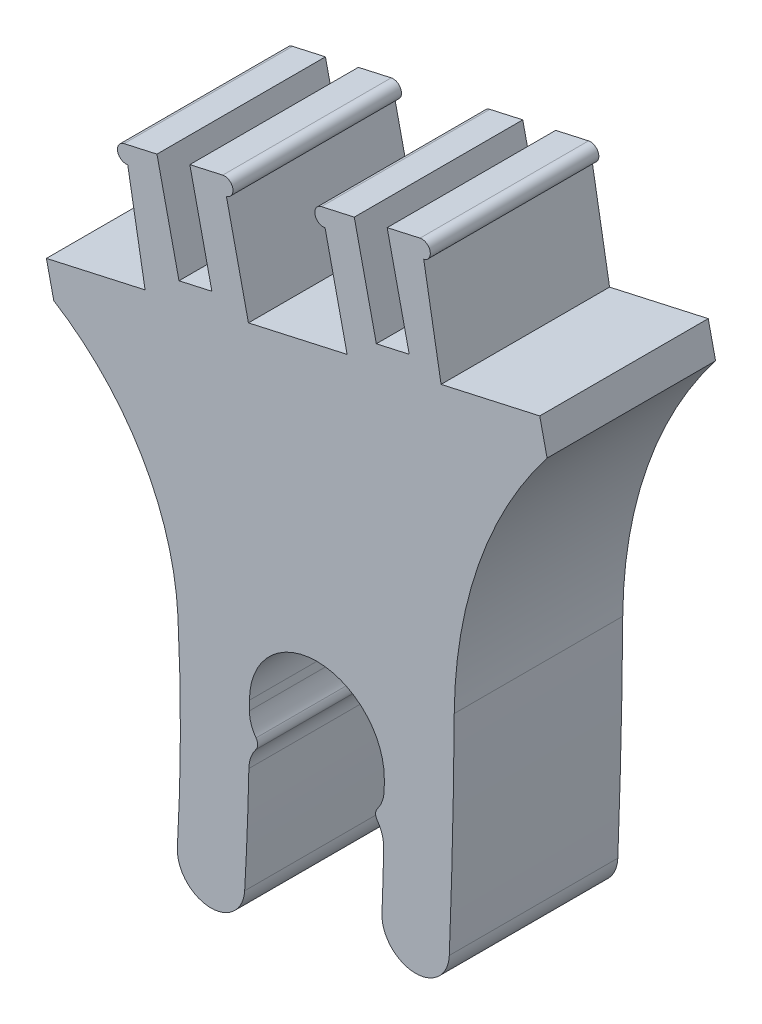
SolidWorks part; units mm, degrees
ref_plane "Front Plane" through (0, 0, 0) normal (0, 0, 1) x (1, 0, 0)
ref_plane "Top Plane" through (0, 0, 0) normal (0, 1, 0) x (1, 0, 0)
ref_plane "Right Plane" through (0, 0, 0) normal (1, 0, 0) x (0, 0, -1)
sketch "Sketch1" plane through (0, 0, 0) normal (0, 0, 1) x (1, 0, 0)
  line L0 (46.3286, 67.6651) -> (48.3537, 68.1177)
  line L1 (39.9639, 81.6128) -> (47.8164, 83.3676)
  line L3 (40.2311, 66.3025) -> (42.2676, 66.7576)
  arc A0 (46.4563, 72.4818) -> (46.4528, 71.6895) centre (-44.4563, 72.4818) cw
  arc A1 (46.4563, 72.4818) -> (42.4563, 72.4818) centre (44.4563, 72.4818) ccw
  arc A3 (42.2676, 66.7576) -> (42.447, 71.2127) centre (-44.4563, 72.4818) ccw
  arc A4 (47.8164, 83.3676) -> (48.3537, 68.1177) centre (-44.4563, 72.4818) cw
  arc A5 (40.2311, 66.3025) -> (39.9639, 81.6128) centre (-44.4563, 72.4818) ccw
  arc A6 (47.8164, 83.3676) -> (48.1264, 64.6591) centre (-44.4563, 72.4818) cw construction
  arc A7 (45.8301, 83.1333) -> (46.1335, 64.8275) centre (-44.4563, 72.4818) cw construction
  arc A8 (42.2258, 66.157) -> (41.9523, 81.8279) centre (-44.4563, 72.4818) ccw construction
  circle A9 centre (44.4563, 72.4818) radius 2 construction
  arc A10 (42.4529, 71.7127) -> (42.447, 71.2127) centre (42.4503, 71.4627) cw
  arc A11 (46.4528, 71.6895) -> (46.4471, 71.1896) centre (46.4503, 71.4395) ccw
  arc A12 (42.4529, 71.7127) -> (42.4563, 72.4818) centre (-44.4563, 72.4818) ccw
  arc A13 (46.4471, 71.1896) -> (46.3286, 67.6651) centre (-44.4563, 72.4818) cw
  dimension "D1" = 4
  dimension "D5" = 0.25
  dimension "D2" = 15
  dimension "D3" = 2
  dimension "D4" = 2
extrude "Boss-Extrude1" add sketch "Sketch1" along normal blind 5
fillet "Fillet1" radius 1 4 edges at (46.4471, 71.1896, 2.5) (46.4528, 71.6895, 2.5) (42.447, 71.2127, 2.5) (42.4529, 71.7127, 2.5)
fillet "Fillet2" radius 1 4 edges at (48.3537, 68.1177, 2.5) (46.3286, 67.6651, 2.5) (42.2676, 66.7576, 2.5) (40.2311, 66.3025, 2.5)
sketch "Sketch2" plane through (0, 0, 5) normal (0, 0, 1) x (1, 0, 0)
  line L1 (39.702, 79.5049) -> (38.8442, 84.4366)
  line L2 (42.4262, 82.1631) -> (41.772, 85.0908)
  line L3 (38.8442, 84.4366) -> (41.772, 85.0908)
  line L5 (48.4854, 81.4678) -> (47.6275, 86.3994)
  line L6 (45.354, 82.8173) -> (44.6998, 85.7451)
  line L7 (47.6275, 86.3994) -> (44.6998, 85.7451)
  line L8 (47.8164, 83.3676) -> (39.9639, 81.6128) construction
  line L9 (41.772, 85.0908) -> (44.6998, 85.7451) construction
  line L10 (44.6998, 85.7451) -> (44.9137, 83.7227) construction
  line L11 (43.2359, 85.418) -> (43.8901, 82.4902) construction
  line L12 (42.4262, 82.1631) -> (40.3174, 67.6268)
  line L13 (45.354, 82.8173) -> (48.3867, 68.8877)
  arc A0 (40.3174, 67.6268) -> (39.702, 79.5049) centre (-14.2779, 70.7535) ccw
  arc A1 (48.4854, 81.4678) -> (48.3867, 68.8877) centre (-155.3783, 76.7758) cw
  arc A2 (40.3174, 67.6268) -> (39.9639, 81.6128) centre (-44.4563, 72.4818) ccw construction
  arc A3 (48.3867, 68.8877) -> (47.8164, 83.3676) centre (-44.4563, 72.4818) ccw construction
  dimension "D1" = 3
  dimension "D2" = 3
  dimension "D3" = 3
extrude "Boss-Extrude2" add sketch "Sketch2" against normal blind 5
sketch "Sketch3" plane through (0, 0, 5) normal (0, 0, 1) x (1, 0, 0)
  line L0 (38.7351, 84.9245) -> (41.6629, 85.5788)
  line L1 (41.772, 85.0908) -> (38.8442, 84.4366) construction
  line L2 (38.7897, 84.6806) -> (41.7175, 85.3348) construction
  line L3 (44.3263, 80.5383) -> (42.6914, 87.8542) construction
  line L4 (38.7351, 84.9245) -> (38.8442, 84.4366) construction
  line L5 (41.6629, 85.5788) -> (41.772, 85.0908) construction
  line L7 (45.354, 82.8173) -> (42.4262, 82.1631) construction
  line L8 (44.5907, 86.2331) -> (44.6998, 85.7451) construction
  line L9 (47.5185, 86.8873) -> (47.6275, 86.3994) construction
  line L10 (47.573, 86.6434) -> (44.6452, 85.9891) construction
  line L11 (47.5185, 86.8873) -> (44.5907, 86.2331)
  arc A0 (38.7351, 84.9245) -> (38.8442, 84.4366) centre (38.7897, 84.6806) ccw
  arc A1 (41.6629, 85.5788) -> (41.772, 85.0908) centre (41.7175, 85.3348) cw
  arc A2 (44.5907, 86.2331) -> (44.6998, 85.7451) centre (44.6452, 85.9891) ccw
  arc A3 (47.5185, 86.8873) -> (47.6275, 86.3994) centre (47.573, 86.6434) cw
  point P11 (43.8901, 82.4902)
  line M4 (47.6275, 86.3994) -> (44.6998, 85.7451)
  line M8 (41.772, 85.0908) -> (38.8442, 84.4366)
  dimension "D1" = 0.5
extrude "Boss-Extrude3" add sketch "Sketch3" against normal blind 5 contours A1 L0 A0 M8 | A3 L11 A2 M4 region at (40.2536, 85.0077, 5) region at (46.1091, 86.3162, 5)
sketch "Sketch4" plane through (0, 0, 5) normal (0, 0, 1) x (1, 0, 0)
  line L0 (39.7111, 85.1426) -> (40.3653, 82.2148)
  line L1 (44.3263, 80.5383) -> (-10860.1634, 48876.9737) construction
  line L2 (40.3653, 82.2148) -> (41.3413, 82.4329)
  line L3 (40.687, 85.3607) -> (41.3413, 82.4329)
  line L4 (40.199, 85.2517) -> (41.3413, 82.4329) construction
  line L5 (40.3653, 82.2148) -> (40.199, 85.2517) construction
  line L6 (38.7351, 84.9245) -> (41.6629, 85.5788) construction
  line L7 (39.7111, 85.1426) -> (40.687, 85.3607)
  line L8 (45.354, 82.8173) -> (42.4262, 82.1631) construction
  line L9 (47.1968, 83.7415) -> (46.0546, 86.5602) construction
  line L10 (46.0546, 86.5602) -> (46.2209, 83.5234) construction
  line L11 (46.5426, 86.6693) -> (45.5666, 86.4512)
  line L12 (45.5666, 86.4512) -> (46.2209, 83.5234)
  line L13 (47.1968, 83.7415) -> (46.2209, 83.5234)
  line L14 (46.5426, 86.6693) -> (47.1968, 83.7415)
  line L15 (40.199, 85.2517) -> (40.8533, 82.3239) construction
  point P1 (40.199, 85.2517)
  point P12 (43.8901, 82.4902)
  dimension "D1" = 1
  dimension "D2" = 3
extrude "Cut-Extrude1" cut sketch "Sketch4" against normal blind 5
sketch "Sketch5" plane through (0, 0, 5) normal (0, 0, 1) x (1, 0, 0)
  line L0 (39.3589, 81.4776) -> (36.4311, 80.8233)
  line L1 (48.1422, 83.4404) -> (51.07, 84.0947)
  line L2 (45.354, 82.8173) -> (42.4262, 82.1631) construction
  line L3 (40.3336, 73.5826) -> (44.0319, 76.9086)
  line L4 (44.0319, 76.9086) -> (48.5331, 75.177)
  line L5 (48.1422, 83.4404) -> (46.3628, 81.8401)
  line L6 (46.3628, 81.8401) -> (39.3589, 81.4776)
  line L7 (36.4311, 80.8233) -> (36.6492, 79.8474)
  line L8 (51.2881, 83.1187) -> (51.07, 84.0947)
  line L9 (38.8442, 84.4366) -> (39.702, 79.5049) construction
  line L10 (48.4854, 81.4678) -> (47.6275, 86.3994) construction
  arc A0 (40.3336, 73.5826) -> (36.6492, 79.8474) centre (32.4728, 73.1754) ccw
  arc A1 (40.3174, 67.6268) -> (39.702, 79.5049) centre (-14.2779, 70.7535) ccw construction
  arc A2 (48.5331, 75.177) -> (51.2881, 83.1187) centre (61.6538, 75.0741) cw
  arc A3 (48.3867, 68.8877) -> (48.4854, 81.4678) centre (-155.3783, 76.7758) ccw construction
  dimension "D1" = 1
extrude "Boss-Extrude4" add sketch "Sketch5" against normal blind 5
